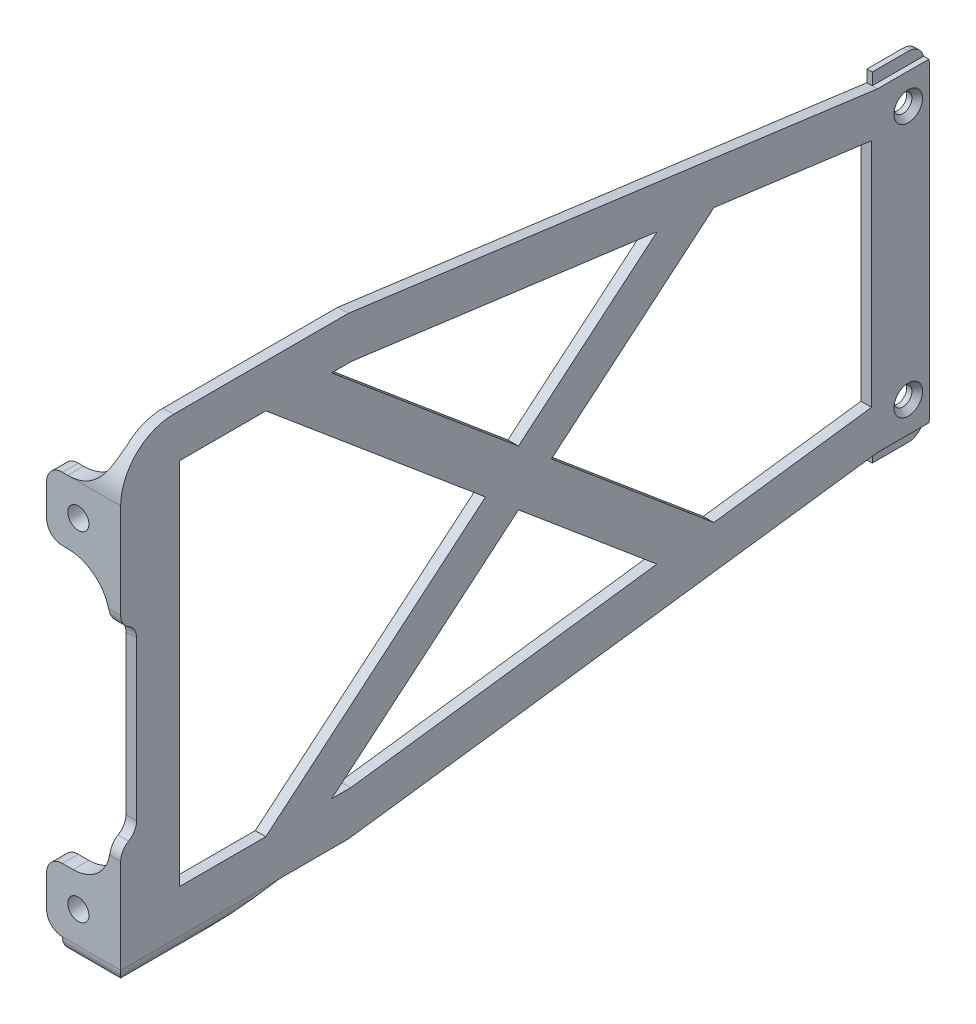
SolidWorks part; units mm, degrees
ref_plane "Front Plane" through (0, 0, 0) normal (0, 0, 1) x (1, 0, 0)
ref_plane "Top Plane" through (0, 0, 0) normal (0, 1, 0) x (1, 0, 0)
ref_plane "Right Plane" through (0, 0, 0) normal (1, 0, 0) x (0, 0, -1)
sketch "Sketch1" plane through (0, 0, 0) normal (1, 0, 0) x (0, 0, -1)
  line L1 (36.7947, 29.75) -> (46.5947, 29.75)
  line L2 (36.7947, 29.75) -> (36.7947, -29.75)
  line L3 (36.7947, -29.75) -> (46.5947, -29.75)
  line L4 (46.5947, 29.75) -> (46.5947, -29.75)
  point P4 (46.5947, 0)
  dimension "D1" = 59.5
  dimension "D2" = 9.8
extrude "Boss-Extrude1" add sketch "Sketch1" along normal blind 2
sketch "Sketch2" plane through (0, 0, 0) normal (1, 0, 0) x (0, 0, -1)
  line L0 (36.7947, 29.75) -> (36.7947, -29.75) construction
  line L1 (36.7947, 32) -> (46.5947, 32)
  line L2 (36.7947, 32) -> (36.7947, -32)
  line L3 (36.7947, -32) -> (46.5947, -32)
  line L4 (46.5947, 32) -> (46.5947, -32)
  line L5 (46.5947, -29.75) -> (46.5947, 29.75) construction
  point P8 (46.5947, 0)
  dimension "D1" = 64
extrude "Boss-Extrude2" add sketch "Sketch2" along normal blind 1
fillet "Fillet1" radius 3 2 edges at (0.5, -32, -46.5947) (0.5, 32, -46.5947)
sketch "Sketch3" plane through (0, 0, 0) normal (1, 0, 0) x (0, 0, -1)
  line L0 (36.7947, 29.75) -> (-63.2053, 43)
  line L2 (-63.2053, -43) -> (36.7947, -29.75)
  line L3 (36.7947, -29.75) -> (36.7947, 29.75)
  line L4 (46.4995, 29.75) -> (36.7947, 29.75) construction
  line L5 (36.7947, 32) -> (36.7947, 29.75) construction
  line L6 (-63.2053, 0) -> (36.7947, 0) construction
  line L8 (-63.2053, 43) -> (-103.2053, 43)
  line L10 (-63.2053, -43) -> (-103.2053, -43)
  line L11 (-103.2053, 43) -> (-103.2053, -43)
  dimension "D1" = 86
  dimension "D2" = 100
  dimension "D3" = 40
extrude "Boss-Extrude3" add sketch "Sketch3" along normal blind 2
sketch "Sketch4" plane through (0, 0, 103.2053) normal (0, 0, 1) x (1, 0, 0)
  line L0 (0, 43) -> (0, -43) construction
  line L1 (2, -43) -> (-9, -43)
  line L2 (2, -43) -> (2, -31)
  line L3 (-7, -31) -> (-9, -31)
  line L4 (-12, -40) -> (-12, -34)
  line L5 (2, -31) -> (2, -23)
  line L6 (2, 43) -> (2, -43) construction
  line L7 (2, -23) -> (0, -23)
  line L8 (0, -23) -> (0, -24)
  circle A0 centre (-6, -37) radius 2
  arc A1 (0, -24) -> (-7, -31) centre (-7, -24) cw
  arc A2 (-9, -43) -> (-12, -40) centre (-9, -40) cw
  arc A3 (-9, -31) -> (-12, -34) centre (-9, -34) ccw
  point P16 (0, -31)
  point P19 (-12, -43)
  point P22 (-12, -31)
  dimension "D6" = 7
  dimension "D7" = 3
  dimension "D8" = 4
  dimension "D1" = 6
  dimension "D2" = 6
  dimension "D3" = 12
  dimension "D4" = 14
  dimension "D5" = 8
extrude "Boss-Extrude4" add sketch "Sketch4" along normal blind 3
fillet "Fillet2" radius 3 1 edges at (1, -23, 103.2053)
fillet "Fillet3" radius 3 1 edges at (1, -23, 106.2053)
sketch "Sketch5" plane through (0, 0, 103.2053) normal (0, 0, 1) x (1, 0, 0)
  line L0 (2, 43) -> (2, -20) construction
  line L1 (-8, 33) -> (-9, 33)
  line L2 (2, 33) -> (2, 21)
  line L3 (-8, 21) -> (-9, 21)
  line L4 (-12, 30) -> (-12, 24)
  line L5 (0, 43) -> (0, -20) construction
  line L6 (2, 43) -> (0, 43) construction
  line L7 (2, 33) -> (2, 43)
  line L8 (2, 43) -> (0, 43)
  line L9 (0, 43) -> (0, 41)
  line L10 (2, 21) -> (2, 12.9)
  line L11 (2, 12.9) -> (0, 12.9)
  line L12 (0, 12.9) -> (0, 13)
  circle A0 centre (-6, 27) radius 2
  arc A1 (-9, 21) -> (-12, 24) centre (-9, 24) cw
  arc A2 (-9, 33) -> (-12, 30) centre (-9, 30) ccw
  arc A3 (0, 13) -> (-8, 21) centre (-8, 13) ccw
  arc A4 (0, 41) -> (-8, 33) centre (-8, 41) cw
  point P14 (-12, 21)
  point P17 (-12, 33)
  point P27 (0, 21)
  point P30 (0, 33)
  point P31 (0, 0)
  dimension "D6" = 3
  dimension "D8" = 8
  dimension "D10" = 4
  dimension "D1" = 14
  dimension "D2" = 6
  dimension "D3" = 16
  dimension "D4" = 10
  dimension "D5" = 12
  dimension "D7" = 8.1
  dimension "D9" = 12
extrude "Boss-Extrude5" add sketch "Sketch5" along normal blind 3
fillet "Fillet4" radius 10 1 edges at (1, 43, 106.2053)
fillet "Fillet6" radius 3 1 edges at (1, 12.9, 103.2053)
fillet "Fillet7" radius 3 1 edges at (1, 12.9, 106.2053)
sketch "Sketch6" plane through (0, -43, 0) normal (0, -1, 0) x (1, 0, 0)
  line L0 (2, 106.2053) -> (-9, 106.2053)
  line L1 (-9, 106.2053) -> (-9, 103.2053)
  line L2 (-9, 103.2053) -> (0, 76.2053)
  line L3 (0, 103.2053) -> (0, 63.2053) construction
  line L4 (0, 76.2053) -> (2, 76.2053)
  line L5 (2, 106.2053) -> (2, 63.2053) construction
  line L6 (2, 76.2053) -> (2, 106.2053)
  dimension "D1" = 30
extrude "Boss-Extrude6" add sketch "Sketch6" along normal blind 3
chamfer "Chamfer1" distance 3 angle 80 1 edges at (1, -46, 76.2053) first distance on face at (1, -44.5, 76.2053)
fillet "Fillet10" radius 3 2 edges at (2, -46, 99.7122) (-3.5, -46, 106.2053)
sketch "Sketch7" plane through (2, 0, 0) normal (1, 0, 0) x (0, 0, -1)
  line L0 (35.6507, 21.8317) -> (35.6507, -21.799)
  line L1 (35.6507, -21.799) -> (-62.7281, -34.8342)
  line L2 (-62.7281, -34.8342) -> (-95.0911, -34.8342)
  line L3 (-95.0911, -34.8342) -> (-95.0911, 34.8342)
  line L4 (-95.0911, 34.8342) -> (-62.4813, 34.8342)
  line L5 (-62.4813, 34.8342) -> (35.6507, 21.8317)
  line L6 (36.7947, 29.75) -> (-63.2053, 43) construction
  line L7 (-63.2053, -43) -> (36.7947, -29.75) construction
  point P10 (-95.0911, 0)
  dimension "D1" = 8
extrude "Cut-Extrude1" cut sketch "Sketch7" against normal through all
sketch "Sketch8" plane through (2, 0, 0) normal (1, 0, 0) x (0, 0, -1)
  line L0 (-78.7862, 34.8342) -> (-37.2725, 0)
  line L1 (-62.4813, 34.8342) -> (-95.0911, 34.8342) construction
  line L4 (5.8569, -25.7466) -> (-24.8267, 0)
  line L5 (-66.3405, 34.8342) -> (-78.7862, 34.8342)
  line L6 (1.1, 0) -> (-1.1, 0) construction
  line L7 (5.8569, 25.7466) -> (-24.8267, 0)
  line L9 (-78.7862, -34.8342) -> (-37.2725, 0)
  line L10 (-66.3405, -34.8342) -> (-78.7862, -34.8342)
  line L11 (-31.0496, 5.2216) -> (-4.8916, 27.1708)
  line L12 (-31.0496, -5.2216) -> (-4.8916, -27.1708)
  line L13 (-31.0496, 5.2216) -> (-66.3405, 34.8342)
  line L14 (-31.0496, -5.2216) -> (-66.3405, -34.8342)
  line L15 (-4.8916, -27.1708) -> (-1.5622, -29.9645)
  line L16 (-1.5622, -29.9645) -> (8.6783, -28.114)
  line L17 (8.6783, -28.114) -> (5.8569, -25.7466)
  line L18 (-4.8916, 27.1708) -> (-2.9024, 28.7966)
  line L19 (-2.9024, 28.7966) -> (7.7751, 27.6653)
  line L20 (7.7751, 27.6653) -> (5.8569, 25.7466)
  dimension "D1" = 8
  dimension "D2" = 40
extrude "Boss-Extrude7" add sketch "Sketch8" against normal up to surface (2 mm away) up to face at (0, 0.0054, 40.6817)
sketch "Sketch9" plane through (2, 0, 0) normal (1, 0, 0) x (0, 0, -1)
  line L0 (42.5947, 24) -> (42.5947, -24) construction
  line L2 (46.5947, -29) -> (46.5947, 29) construction
  circle A0 centre (42.5947, 24) radius 1.7
  circle A1 centre (42.5947, -24) radius 1.7
  point P4 (42.5947, 0)
  dimension "D1" = 3.4
  dimension "D2" = 4
  dimension "D3" = 48
extrude "Cut-Extrude2" cut sketch "Sketch9" against normal through all
chamfer "Chamfer2" distance 1 angle 45 2 edges at (2, -24, -44.2947) (2, 24, -44.2947)
